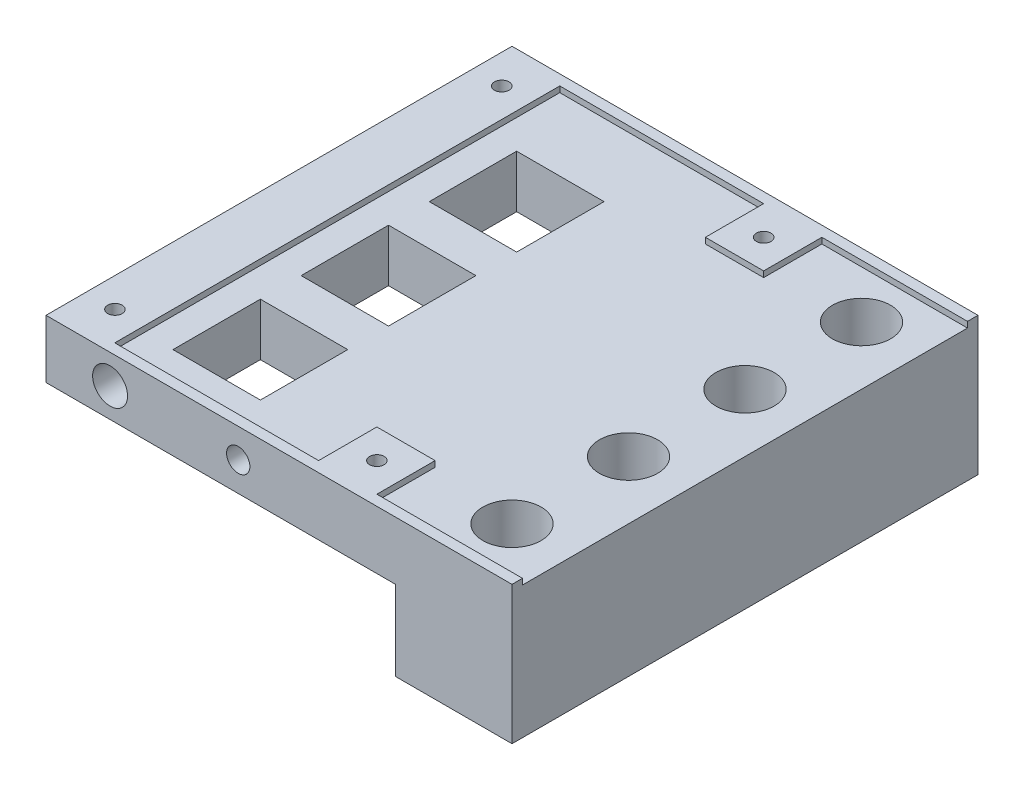
SolidWorks part; units mm, degrees
ref_plane "Front Plane" through (0, 0, 0) normal (0, 0, 1) x (1, 0, 0)
ref_plane "Top Plane" through (0, 0, 0) normal (0, 1, 0) x (1, 0, 0)
ref_plane "Right Plane" through (0, 0, 0) normal (1, 0, 0) x (0, 0, -1)
sketch "Sketch1" plane through (0, 0, 0) normal (0, 1, 0) x (1, 0, 0)
  line L1 (-77.5607, 49.5304) -> (2.4393, 49.5304)
  line L2 (-77.5607, 49.5304) -> (-77.5607, -30.4696)
  line L3 (-77.5607, -30.4696) -> (2.4393, -30.4696)
  line L4 (2.4393, 49.5304) -> (2.4393, -30.4696)
  dimension "D1" = 80
  dimension "D2" = 80
extrude "Boss-Extrude1" add sketch "Sketch1" along normal blind 23.7
sketch "Sketch2" plane through (0, 23.7, 0) normal (0, 1, 0) x (1, 0, 0)
  line L0 (2.4393, -30.4696) -> (2.4393, 49.5304) construction
  line L1 (2.4393, -28.6696) -> (-22.5607, -28.6696)
  line L2 (2.4393, -28.6696) -> (2.4393, 47.7304)
  line L3 (2.4393, 47.7304) -> (-22.5607, 47.7304)
  line L4 (-67.5607, -28.6696) -> (-67.5607, 47.7304)
  line L5 (-77.5607, 49.5304) -> (-77.5607, -30.4696) construction
  line L6 (-77.5607, 9.5304) -> (2.4393, 9.5304) construction
  line L8 (-32.5607, 47.7304) -> (-32.5607, 37.7304)
  line L9 (-32.5607, 37.7304) -> (-22.5607, 37.7304)
  line L10 (-22.5607, 47.7304) -> (-22.5607, 37.7304)
  line L11 (-32.5607, -18.6696) -> (-22.5607, -18.6696)
  line L12 (-22.5607, -28.6696) -> (-22.5607, -18.6696)
  line L14 (-32.5607, -28.6696) -> (-32.5607, -18.6696)
  line L15 (-32.5607, -28.6696) -> (-67.5607, -28.6696)
  line L16 (-32.5607, 47.7304) -> (-67.5607, 47.7304)
  point P6 (-67.5607, 9.5304)
  point P9 (-77.5607, 9.5304)
  dimension "D1" = 76.4
  dimension "D2" = 10
  dimension "D3" = 10
  dimension "D4" = 10
  dimension "D5" = 35
extrude "Cut-Extrude1" cut sketch "Sketch2" against normal blind 1
sketch "Sketch3" plane through (0, 22.7, 0) normal (0, 1, 0) x (1, 0, 0)
  line L0 (-67.5607, 47.7304) -> (-67.5607, -28.6696) construction
  line L1 (-62.5607, -23.6696) -> (-47.5607, -23.6696)
  line L2 (-62.5607, -23.6696) -> (-62.5607, -8.6696)
  line L3 (-62.5607, -8.6696) -> (-47.5607, -8.6696)
  line L4 (-47.5607, -23.6696) -> (-47.5607, -8.6696)
  line L5 (-22.5607, -28.6696) -> (2.4393, -28.6696) construction
  line L6 (-62.5607, -1.6696) -> (-62.5607, 13.3304)
  line L7 (-62.5607, -1.6696) -> (-47.5607, -1.6696)
  line L8 (-47.5607, -1.6696) -> (-47.5607, 13.3304)
  line L9 (-62.5607, 13.3304) -> (-47.5607, 13.3304)
  line L10 (-62.5607, 20.3304) -> (-62.5607, 35.3304)
  line L11 (-62.5607, 20.3304) -> (-47.5607, 20.3304)
  line L12 (-47.5607, 20.3304) -> (-47.5607, 35.3304)
  line L13 (-62.5607, 35.3304) -> (-47.5607, 35.3304)
  dimension "D1" = 15
  dimension "D2" = 15
  dimension "D3" = 5
  dimension "D4" = 5
  dimension "D5" = 3
extrude "Cut-Extrude2" cut sketch "Sketch3" against normal through all
sketch "Sketch4" plane through (0, 0, 30.4696) normal (0, 0, 1) x (1, 0, 0)
  line L0 (-77.5607, 23.7) -> (2.4393, 23.7) construction
  line L1 (-77.5607, 0) -> (-17.5607, 0)
  line L2 (-77.5607, 0) -> (-77.5607, 13.7)
  line L3 (-77.5607, 13.7) -> (-17.5607, 13.7)
  line L4 (-17.5607, 0) -> (-17.5607, 13.7)
  line L5 (2.4393, 23.7) -> (2.4393, 0) construction
  dimension "D1" = 10
  dimension "D2" = 20
extrude "Cut-Extrude3" cut sketch "Sketch4" against normal through all
sketch "Sketch5" plane through (0, 0, 30.4696) normal (0, 0, 1) x (1, 0, 0)
  line L0 (-77.5607, 23.7) -> (-77.5607, 13.7) construction
  line L1 (-62.5607, 13.7) -> (-62.5607, 22.7) construction
  line L2 (-47.5607, 13.7) -> (-47.5607, 22.7) construction
  circle A0 centre (-66.5607, 18.7) radius 3
  circle A1 centre (-44.5607, 18.7) radius 2
  point P5 (-77.5607, 18.7)
  dimension "D1" = 6
  dimension "D3" = 4
  dimension "D4" = 3
  dimension "D2" = 4
extrude "Cut-Extrude4" cut sketch "Sketch5" against normal through all
sketch "Sketch6" plane through (0, 22.7, 0) normal (0, 1, 0) x (1, 0, 0)
  line L0 (-7.5607, 47.7304) -> (-7.5607, -28.6696) construction
  line L1 (2.4393, 47.7304) -> (-22.5607, 47.7304) construction
  line L2 (-22.5607, -28.6696) -> (2.4393, -28.6696) construction
  line L3 (2.4393, -28.6696) -> (2.4393, 47.7304) construction
  line L4 (-77.5607, -30.4696) -> (2.4393, -30.4696) construction
  point P8 (-7.5607, -20.4696)
  point P9 (-7.5607, -0.4696)
  point P10 (-7.5607, 19.5304)
  point P11 (-7.5607, 39.5304)
  dimension "D1" = 10
  dimension "D2" = 10
  dimension "D3" = 20
  dimension "D4" = 20
  dimension "D5" = 20
hole_wizard "CBORE for M5 Hex Socket Head Cap1" positions "Sketch7" profile "Sketch8" counterbore size "M5" standard "BSI" end condition up to next
sketch "Sketch7" plane through (0, 22.7, 0) normal (0, 1, 0) x (1, 0, 0)
  point P0 (-7.5607, -20.4696)
  point P3 (-7.5607, -0.4696)
  point P6 (-7.5607, 19.5304)
  point P9 (-7.5607, 39.5304)
sketch "Sketch8" plane through (-7.5607, 22.7, 20.4696) normal (1, 0, 0) x (0, 0, 1)
  line L0 (0, 0) -> (0, 22.7)
  line L1 (0, 22.7) -> (2.75, 22.7)
  line L3 (2.75, 22.7) -> (2.75, 15)
  line L4 (2.75, 15) -> (5, 15)
  line L5 (5, 15) -> (5, 0)
  line L7 (5, 0) -> (0, 0)
  line L11 (0, -6.35) -> (0, 107.95) construction
  dimension "Thru Hole Dia." = 5.5
  dimension "Thru Hole Depth" = 22.7
  dimension "C'Bore Dia." = 10
  dimension "C'Bore Depth" = 15
sketch "Sketch9" plane through (0, 23.7, 0) normal (0, 1, 0) x (1, 0, 0)
  line L0 (-32.5607, 37.7304) -> (-32.5607, 47.7304) construction
  line L1 (-22.5607, 37.7304) -> (-32.5607, 37.7304) construction
  line L2 (-77.5607, 9.5304) -> (10.7906, 9.5304) construction
  line L3 (-77.5607, 49.5304) -> (-77.5607, -30.4696) construction
  point P0 (-27.5607, 42.7304)
  point P3 (-32.5607, 42.7304)
  point P4 (-27.5607, -23.6696)
  point P7 (-27.5607, 37.7304)
  point P8 (-72.5233, -23.6696)
  point P14 (-72.5233, 42.7304)
hole_wizard "M3x0.5 Tapped Hole1" positions "Sketch10" profile "Sketch11" tap size "M3x0.5" standard "BSI" end condition up to next
sketch "Sketch10" plane through (0, 23.7, 0) normal (0, 1, 0) x (1, 0, 0)
  point P0 (-27.5607, -23.6696)
  point P3 (-27.5607, 42.7304)
  point P7 (-72.5233, -23.6696)
  point P10 (-72.5233, 42.7304)
sketch "Sketch11" plane through (-27.5607, 23.7, 23.6696) normal (1, 0, 0) x (0, 0, 1)
  line L0 (0, 0) -> (0, 10)
  line L1 (0, 10) -> (1.25, 10)
  line L2 (1.25, 10) -> (1.25, 0)
  line L5 (1.25, 0) -> (0, 0)
  line L11 (0, -6.35) -> (0, 107.95) construction
  dimension "Thru Tap Drill Dia." = 2.5
  dimension "Thru Tap Drill Depth" = 10
cosmetic thread "Hole Thread1" parameters "D2"=3
cosmetic thread "Hole Thread2" parameters "D2"=3
cosmetic thread "Hole Thread3" parameters "D2"=3
cosmetic thread "Hole Thread4" parameters "D2"=3
ref_axis "Axis1" through (-66.5607, 18.7, -49.5304) along (0, 0, 1)
ref_axis "Axis2" through (-44.5607, 18.7, -49.5304) along (0, 0, 1)
sketch "Sketch12" plane through (0, 13.7, 0) normal (0, -1, 0) x (1, 0, 0)
  line L0 (-17.5607, 30.4696) -> (-77.5607, 30.4696) construction
  line L4 (-66.5607, -49.5304) -> (-66.5607, 30.4696) construction
  line L5 (-44.5607, -49.5304) -> (-44.5607, 30.4696) construction
  line L6 (-77.5607, -9.5304) -> (-21.3569, -9.5304) construction
  line L7 (-77.5607, -49.5304) -> (-77.5607, 30.4696) construction
  point P0 (-66.5607, 15.4696)
  point P1 (-44.5607, 15.4696)
  point P4 (0, 0)
  point P5 (-44.5607, -34.5304)
  point P6 (-66.5607, -34.5304)
  dimension "D1" = 15
hole_wizard "M2x0.4 Tapped Hole1" positions "Sketch13" profile "Sketch14" tap size "M2x0.4" standard "BSI" end condition up to next
sketch "Sketch13" plane through (0, 13.7, 0) normal (0, -1, 0) x (-1, 0, 0)
  point P0 (66.5607, -15.4696)
  point P3 (44.5607, -15.4696)
  point P6 (66.5607, 34.5304)
  point P9 (44.5607, 34.5304)
sketch "Sketch14" plane through (-66.5607, 13.7, 15.4696) normal (1, 0, 0) x (0, 0, -1)
  line L0 (0, 0) -> (0, 2)
  line L1 (0, 2) -> (0.8, 2)
  line L2 (0.8, 2) -> (0.8, 0)
  line L5 (0.8, 0) -> (0, 0)
  line L11 (0, -6.35) -> (0, 107.95) construction
  dimension "Thru Tap Drill Dia." = 1.6
  dimension "Thru Tap Drill Depth" = 2
cosmetic thread "Hole Thread5" parameters "D2"=2
cosmetic thread "Hole Thread6" parameters "D2"=2
cosmetic thread "Hole Thread7" parameters "D2"=2
cosmetic thread "Hole Thread8" parameters "D2"=2
